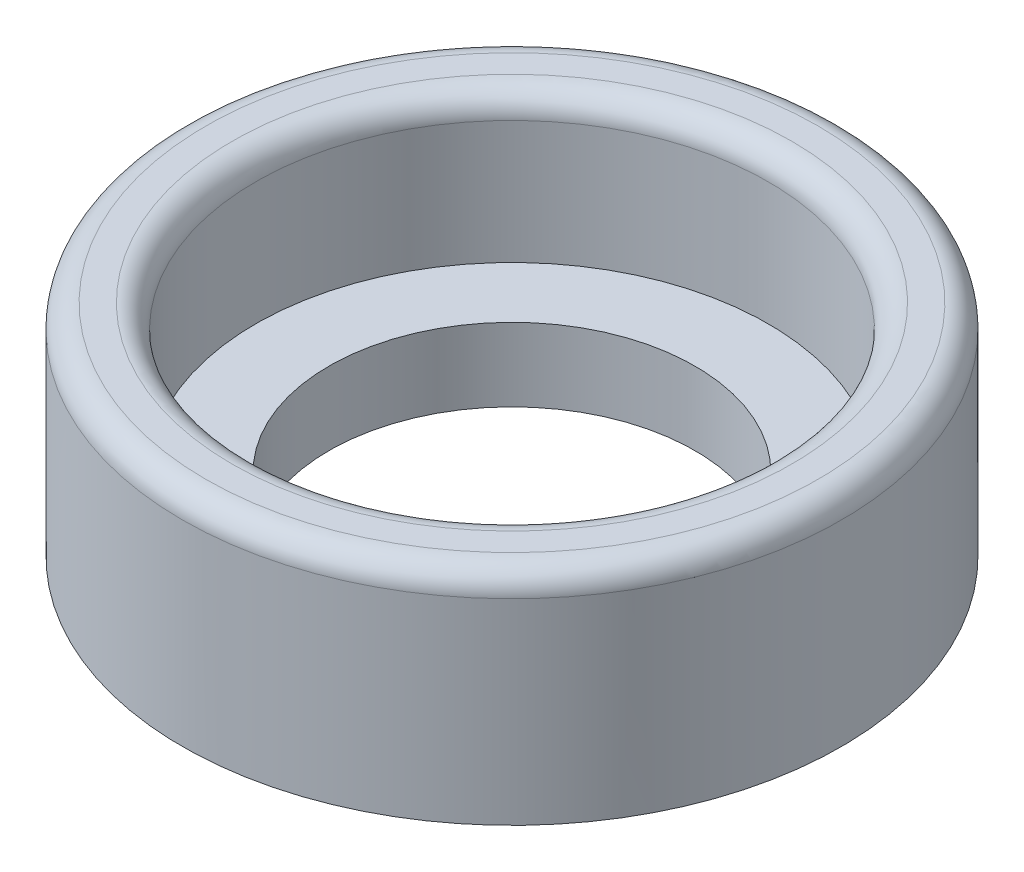
SolidWorks part; units mm, degrees
material "PE High Density"
ref_plane "Front Plane" through (0, 0, 0) normal (0, 0, 1) x (1, 0, 0)
ref_plane "Top Plane" through (0, 0, 0) normal (0, 1, 0) x (1, 0, 0)
ref_plane "Right Plane" through (0, 0, 0) normal (1, 0, 0) x (0, 0, -1)
ref_axis "X-Axis" through (-88.99, 0, 0) along (1, 0, 0)
ref_axis "Y-Axis" through (0, 55, 0) along (0, -1, 0)
ref_axis "Z-Axis" through (0, 0, -88.99) along (0, 0, 1)
sketch "Sketch1" plane through (0, 0, 0) normal (0, 1, 0) x (1, 0, 0)
  circle A0 centre (0, 0) radius 7.1438
  dimension "D1" = 14.2875
extrude "Boss-Extrude1" add sketch "Sketch1" along normal blind 4.7625
hole_wizard "CBORE for #00 Binding Head Machine Screw1" positions "Sketch2" profile "Sketch3" counterbore size "#00" standard "ANSI Inch" end condition through all
sketch "Sketch2" plane through (0, 4.7625, 0) normal (0, 1, 0) x (1, 0, 0)
  point P0 (0, 0)
sketch "Sketch3" plane through (0, 4.7625, 0) normal (1, 0, 0) x (0, 0, 1)
  line L0 (0, 0) -> (0, 4.7625)
  line L1 (0, 4.7625) -> (3.9687, 4.7625)
  line L3 (3.9687, 4.7625) -> (3.9688, 3.175)
  line L4 (3.9688, 3.175) -> (5.5562, 3.175)
  line L5 (5.5562, 3.175) -> (5.5562, 0)
  line L7 (5.5562, 0) -> (0, 0)
  line L11 (0, -6.35) -> (0, 107.95) construction
  dimension "Thru Hole Dia." = 7.9375
  dimension "Thru Hole Depth" = 4.7625
  dimension "C'Bore Dia." = 11.1125
  dimension "C'Bore Depth" = 3.175
fillet "Fillet2" radius 0.508 2 edges at (0, 4.7625, 7.1438) (0, 4.7625, 5.5562)
